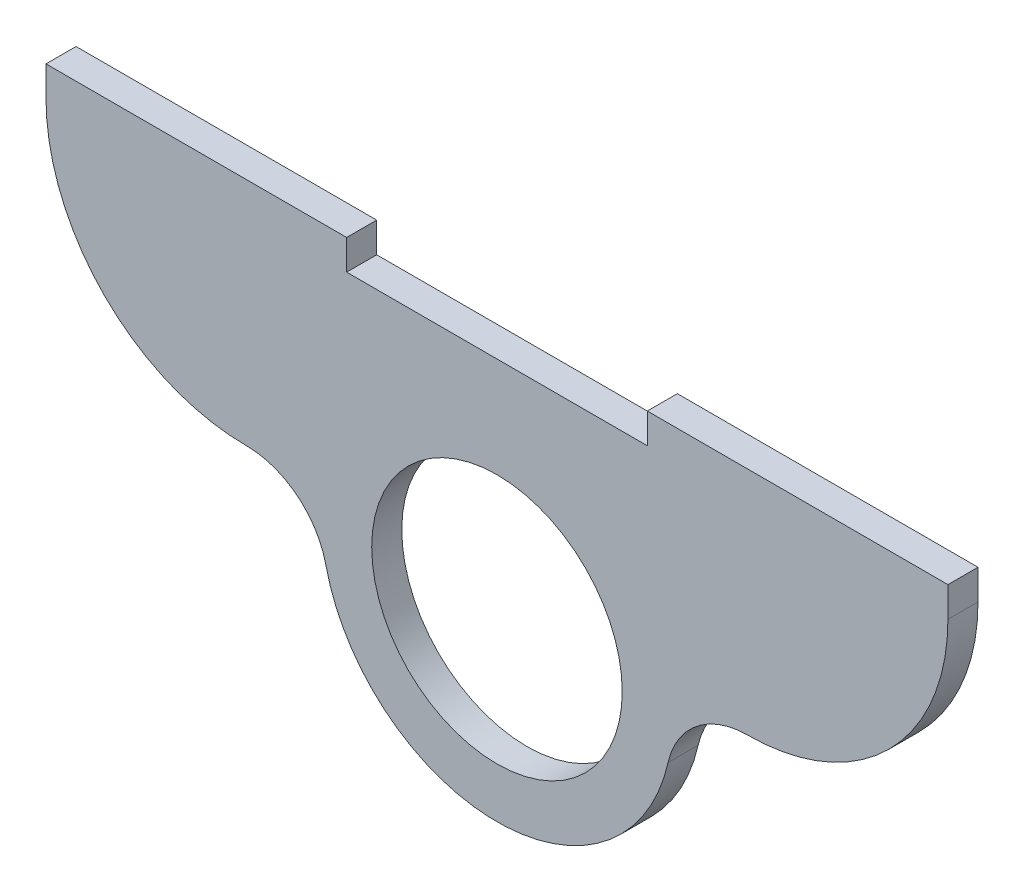
SolidWorks part; units mm, degrees
ref_plane "Front Plane" through (0, 0, 0) normal (0, 0, 1) x (1, 0, 0)
ref_plane "Top Plane" through (0, 0, 0) normal (0, 1, 0) x (1, 0, 0)
ref_plane "Right Plane" through (0, 0, 0) normal (1, 0, 0) x (0, 0, -1)
sketch "Sketch1" plane through (0, 0, 0) normal (0, 0, 1) x (1, 0, 0)
  line L0 (-8.5, 0) -> (8.5, 0) construction
  line L1 (-15, 22.5) -> (15, 22.5)
  line L2 (-45, 22.5) -> (-45, 28.6955) construction
  line L3 (45, 22.5) -> (45, 25.5) construction
  line L4 (-25, 2.5) -> (-49.9345, 2.5) construction
  line L5 (25, 2.5) -> (47.5049, 2.5) construction
  line L8 (-45, 22.5) -> (-45, 25.5)
  line L9 (-45, 25.5) -> (-15, 25.5)
  line L10 (-15, 22.5) -> (-15, 25.5)
  line L12 (45, 22.5) -> (45, 25.5)
  line L13 (45, 25.5) -> (15, 25.5)
  line L14 (15, 22.5) -> (15, 25.5)
  circle A0 centre (-8.5, 0) radius 1.5 construction
  circle A1 centre (8.5, 0) radius 1.5 construction
  circle A2 centre (0, 0) radius 3.5 construction
  circle A3 centre (0, 0) radius 12.5
  arc A4 (-17.0732, -3.8415) -> (17.0732, -3.8415) centre (0, 0) ccw
  arc A5 (-45, 22.5) -> (-25, 2.5) centre (-25, 22.5) ccw
  arc A6 (-17.0732, -3.8415) -> (-25, 2.5) centre (-25, -5.625) ccw
  arc A7 (17.0732, -3.8415) -> (25, 2.5) centre (25, -5.625) cw
  arc A8 (25, 2.5) -> (45, 22.5) centre (25, 22.5) ccw
  point P4 (0, 0)
  point P10 (0, 22.5)
  point P12 (0, 12.5)
  dimension "D1" = 3
  dimension "D3" = 7
  dimension "D5" = 25
  dimension "D9" = 5
  dimension "D2" = 17
  dimension "D4" = 90
  dimension "D6" = 10
  dimension "D7" = 20
  dimension "D8" = 3
extrude "Boss-Extrude1" add sketch "Sketch1" along normal blind 3
